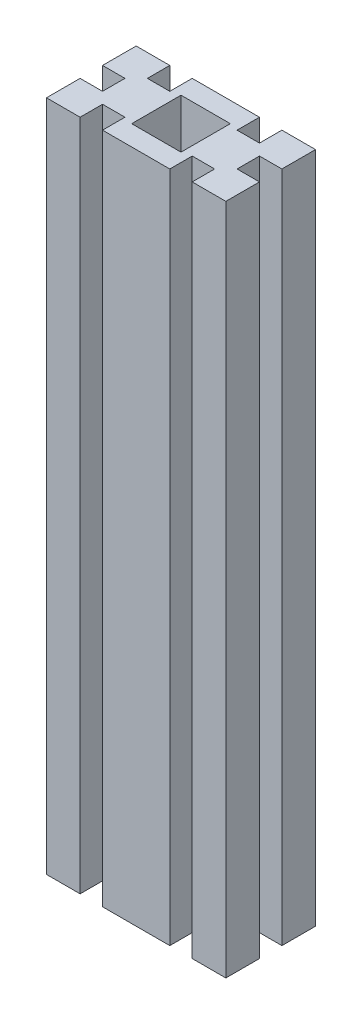
SolidWorks part; units mm, degrees
ref_plane "Front Plane" through (0, 0, 0) normal (0, 0, 1) x (1, 0, 0)
ref_plane "Top Plane" through (0, 0, 0) normal (0, 1, 0) x (1, 0, 0)
ref_plane "Right Plane" through (0, 0, 0) normal (1, 0, 0) x (0, 0, -1)
sketch "Sketch1" plane through (0, 0, 0) normal (0, 1, 0) x (1, 0, 0)
  line L1 (20, -10) -> (-20, -10)
  line L2 (20, -10) -> (20, 10)
  line L3 (20, 10) -> (-20, 10)
  line L4 (-20, -10) -> (-20, 10)
  line L5 (20, -10) -> (-20, 10) construction
  line L6 (20, 10) -> (-20, -10) construction
  point P0 (0, 0)
  dimension "D1" = 20
  dimension "D2" = 40
extrude "Body" add sketch "Sketch1" along normal blind 150
sketch "Sketch2" plane through (0, 150, 0) normal (0, 1, 0) x (1, 0, 0)
  line L0 (20, 10) -> (-20, 10) construction
  line L1 (-12.5, 10) -> (-7.5, 10)
  line L2 (-12.5, 10) -> (-12.5, 5)
  line L3 (-12.5, 5) -> (-7.5, 5)
  line L4 (-7.5, 10) -> (-7.5, 5)
  line L5 (-20, 10) -> (-20, -10) construction
  line L6 (-20, 2.5) -> (-15, 2.5)
  line L7 (-20, 2.5) -> (-20, -2.5)
  line L8 (-20, -2.5) -> (-15, -2.5)
  line L9 (-15, 2.5) -> (-15, -2.5)
  line L10 (-20, -10) -> (20, -10) construction
  line L11 (-12.5, -10) -> (-7.5, -10)
  line L12 (-12.5, -10) -> (-12.5, -5)
  line L13 (-12.5, -5) -> (-7.5, -5)
  line L14 (-7.5, -10) -> (-7.5, -5)
  line L15 (0, -1000) -> (0, 49000) construction
  line L16 (7.5, -10) -> (7.5, -5)
  line L17 (12.5, -5) -> (7.5, -5)
  line L18 (12.5, -10) -> (12.5, -5)
  line L19 (12.5, -10) -> (7.5, -10)
  line L20 (15, 2.5) -> (15, -2.5)
  line L21 (20, -2.5) -> (15, -2.5)
  line L22 (20, 2.5) -> (20, -2.5)
  line L23 (20, 2.5) -> (15, 2.5)
  line L24 (7.5, 10) -> (7.5, 5)
  line L25 (12.5, 5) -> (7.5, 5)
  line L26 (12.5, 10) -> (12.5, 5)
  line L27 (12.5, 10) -> (7.5, 10)
  line L29 (5.5, 5.5) -> (-5.5, 5.5)
  line L30 (5.5, 5.5) -> (5.5, -5.5)
  line L31 (5.5, -5.5) -> (-5.5, -5.5)
  line L32 (-5.5, 5.5) -> (-5.5, -5.5)
  line L33 (5.5, 5.5) -> (-5.5, -5.5) construction
  line L34 (5.5, -5.5) -> (-5.5, 5.5) construction
  point P18 (-15, 0)
  point P35 (0, 0)
  dimension "D1" = 5
  dimension "D2" = 5
  dimension "D3" = 7.5
  dimension "D4" = 11
extrude "Profilage" cut sketch "Sketch2" against normal through all
